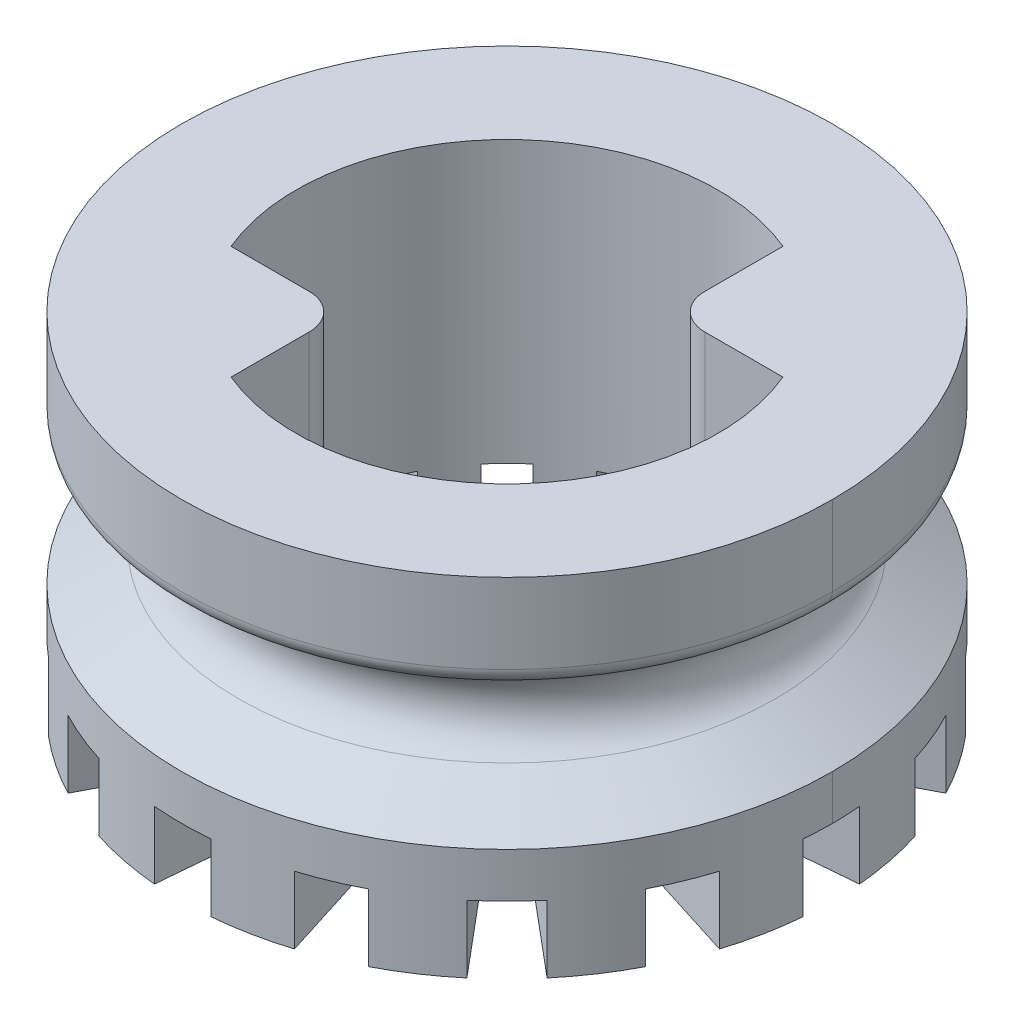
SolidWorks part; units mm, degrees
ref_plane "Front" through (0, 0, 0) normal (0, 0, 1) x (1, 0, 0)
ref_plane "Top" through (0, 0, 0) normal (0, 1, 0) x (1, 0, 0)
ref_plane "Right" through (0, 0, 0) normal (1, 0, 0) x (0, 0, -1)
sketch "Sketch1" plane through (0, 0, 0) normal (0, 1, 0) x (1, 0, 0)
  circle A0 centre (0, 0) radius 3.683
  dimension "D1" = 7.366
extrude "Base-Extrude" add sketch "Sketch1" along normal blind 3.937
sketch "Sketch2" plane through (0, 3.937, 0) normal (0, 1, 0) x (-1, 0, 0)
  circle A0 centre (0, 0) radius 2.3876
  dimension "D1" = 4.7752
extrude "Cut-Extrude1" cut sketch "Sketch2" against normal through all
split line "Split Line1"
sketch "Sketch4" plane through (0, 0, 0) normal (0, 0, 1) x (1, 0, 0)
  line L0 (-0.8167, 2.0955) -> (6.9225, 2.0955) construction
  line L1 (3.683, 2.921) -> (3.0384, 2.5298)
  line L2 (3.683, 0) -> (3.683, 3.937) construction
  line L3 (-3.683, 3.937) -> (3.683, 3.937) construction
  line L4 (3.683, 1.27) -> (3.0384, 1.6612)
  line L5 (0, 0) -> (0, 4.7179) construction
  line L6 (3.683, 2.921) -> (3.683, 1.27)
  arc A0 (3.0384, 2.5298) -> (3.0384, 1.6612) centre (3.302, 2.0955) ccw
  dimension "D4" = 0.508
  dimension "D1" = 1.016
  dimension "D2" = 1.651
  dimension "D3" = 5.588
revolve "Cut-Revolve1" cut sketch "Sketch4" angle 360 about L5
sketch "Sketch5" plane through (16.4943, 0, 2.5829) normal (0, -1, 0) x (1, 0, 0)
  line L0 (-16.4943, -2.5829) -> (-23.5814, -2.5829) construction
  line L1 (-16.4943, -2.5829) -> (-27.4899, -1.6209) construction
  line L2 (-18.8728, -2.3748) -> (-20.1633, -2.2619)
  line L3 (-18.8728, -2.791) -> (-20.1633, -2.9039)
  circle A0 centre (-16.4943, -2.5829) radius 2.3876 construction
  arc A1 (-18.8728, -2.3748) -> (-18.8728, -2.791) centre (-16.4943, -2.5829) ccw
  arc A2 (-20.1773, -2.5829) -> (-12.8113, -2.5829) centre (-16.4943, -2.5829) ccw construction
  arc A3 (-20.1633, -2.2619) -> (-20.1633, -2.9039) centre (-16.4943, -2.5829) ccw
  dimension "D1" = 10
extrude "Cut-Extrude2" cut sketch "Sketch5" against normal blind 0.762
pattern_circular "CirPattern1" count 16 every 22.5 about axis through (0, 3.937, 0) along (0, -1, 0) of "Cut-Extrude2"
sketch "Sketch6" plane through (0, 3.937, 0) normal (0, 1, 0) x (-1, 0, 0)
  line L0 (0, 0) -> (-4.1536, 0) construction
  line L1 (0, 0) -> (0, -5.1565) construction
  line L2 (-0.9208, -2.2029) -> (-0.9207, -0.9208)
  line L3 (-0.9207, -0.9208) -> (-2.2029, -0.9208)
  line L4 (0, 0) -> (-3.0791, 3.0791) construction
  line L5 (2.2029, 0.9207) -> (0.9208, 0.9207)
  line L6 (0.9208, 0.9207) -> (0.9208, 2.2029)
  circle A0 centre (0, 0) radius 2.3876 construction
  arc A1 (-2.2029, -0.9208) -> (-0.9208, -2.2029) centre (0, 0) ccw
  arc A2 (2.2029, 0.9207) -> (0.9208, 2.2029) centre (0, 0) ccw
  dimension "D1" = 0.9207
  dimension "D2" = 45
extrude "Boss-Extrude1" add sketch "Sketch6" against normal up to surface (3.175 mm away)
fillet "Fillet1" radius 0.3969 2 edges at (-0.9208, 2.3495, 0.9207) (0.9207, 2.3495, -0.9208)
fillet "Fillet2" radius 0.1984 2 edges at (0, 2.921, 3.683) (0, 2.921, -3.683)
